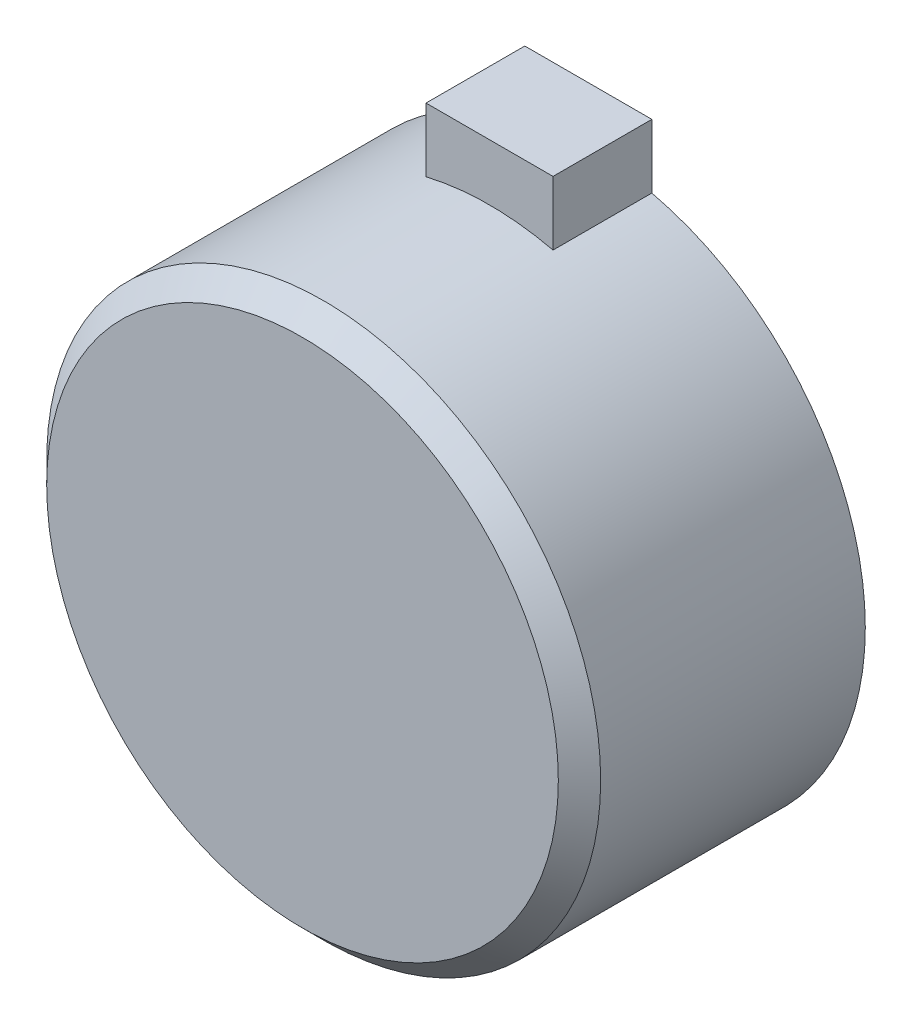
SolidWorks part; units mm, degrees
ref_plane "Front Plane" through (0, 0, 0) normal (0, 0, 1) x (1, 0, 0)
ref_plane "Top Plane" through (0, 0, 0) normal (0, 1, 0) x (1, 0, 0)
ref_plane "Right Plane" through (0, 0, 0) normal (1, 0, 0) x (0, 0, -1)
sketch "SK_Body" plane through (0, 0, 0) normal (0, 1, 0) x (1, 0, 0)
  line L0 (0, -10) -> (0, 50.5) construction
  line L1 (0, 0) -> (36.25, 0)
  line L2 (36.25, 0) -> (39.25, 3)
  line L3 (39.25, 3) -> (39.25, 40.5)
  line L4 (39.25, 40.5) -> (36.25, 40.5)
  line L5 (36.25, 40.5) -> (0, 40.5)
  line L6 (0, 40.5) -> (0, 0)
  dimension "P1" = 10
  dimension "P2" = 50.5
  dimension "R_front" = 36.25
  dimension "P4" = 39.25
  dimension "P5" = 3
  dimension "R_body" = 39.25
  dimension "L_body" = 40.5
  dimension "P8" = 36.25
  dimension "P9" = 40.5
  dimension "P10" = 40.5
revolve "Housing_Body" add sketch "SK_Body" angle 360 about L0
ref_plane "PL_Rear" through (0, 0, -40.5) normal (0, 0, 1) x (1, 0, 0)
sketch "SK_RearHole" plane through (0, 0, -40.5) normal (0, 0, 1) x (1, 0, 0)
  circle A0 centre (33, 0) radius 1.25
  dimension "D_rh" = 2.5
  dimension "R_rh" = 33
extrude "Rear_Tapped_Hole" cut sketch "SK_RearHole" along normal blind 8
ref_axis "AX_Joint" through (0, 0, -42.525) along (0, 0, 1)
pattern_circular "Rear_Hole_Pattern" count 6 over 360 about axis through (0, 0, -42.525) along (0, 0, 1) of "Rear_Tapped_Hole"
sketch "SK_Connector" plane through (0, 0, -40.5) normal (0, 0, 1) x (1, 0, 0)
  line L0 (-9, 35.25) -> (9, 35.25)
  line L1 (9, 35.25) -> (9, 47.25)
  line L2 (9, 47.25) -> (-9, 47.25)
  line L3 (-9, 47.25) -> (-9, 35.25)
  dimension "P1" = 9
  dimension "P2" = 35.25
  dimension "P3" = 9
  dimension "P4" = 35.25
  dimension "P5" = 9
  dimension "P6" = 47.25
  dimension "P7" = 9
  dimension "P8" = 47.25
extrude "Connector_Zone" add sketch "SK_Connector" along normal blind 14
equation "\"D_act\" = 78.5"
equation "\"L_housing\" = 40.5"
equation "\"PCD_rear\" = 66"
equation "\"D_rear_hole\" = 2.5"
equation "\"D_bearing_boss\" = 46"
equation "\"R_front@SK_Body\" = \"D_act\"/2-3.0"
equation "\"R_body@SK_Body\" = \"D_act\"/2"
equation "\"L_body@SK_Body\" = \"L_housing\""
equation "\"D_rh@SK_RearHole\" = \"D_rear_hole\""
equation "\"R_rh@SK_RearHole\" = \"PCD_rear\"/2"
